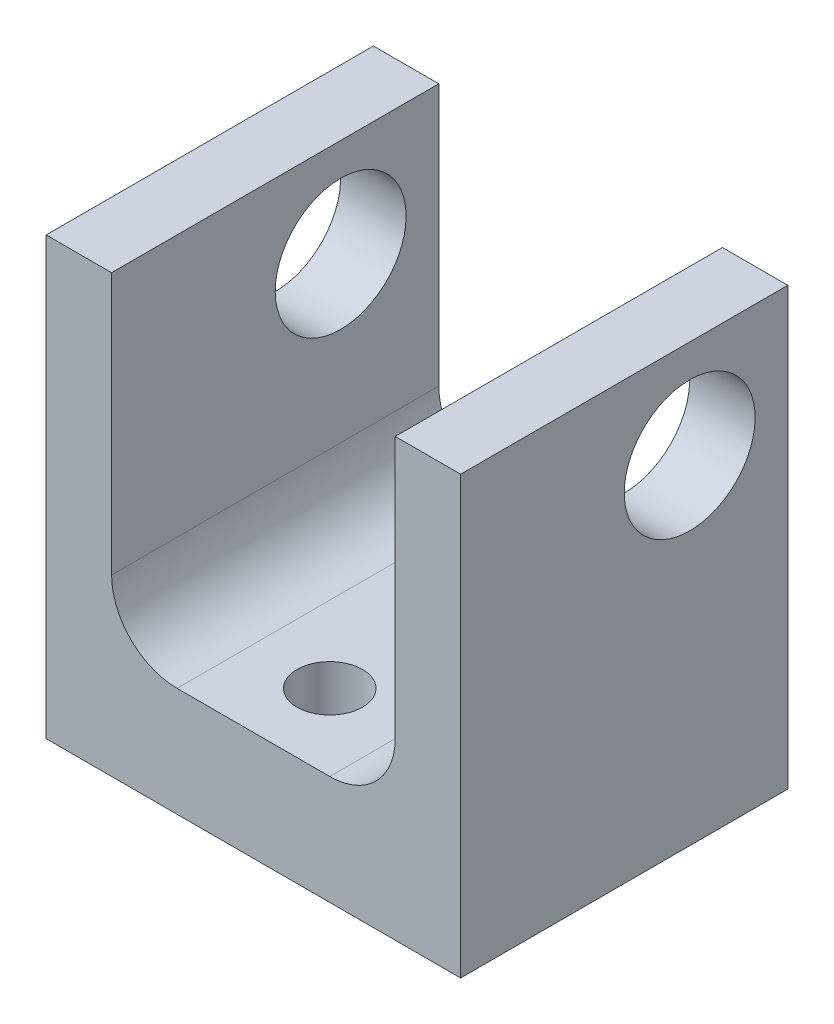
SolidWorks part; units mm, degrees
material "POM 乙缩醛共聚物"
ref_plane "前视基准面" through (0, 0, 0) normal (0, 0, 1) x (1, 0, 0)
ref_plane "上视基准面" through (0, 0, 0) normal (0, 1, 0) x (1, 0, 0)
ref_plane "右视基准面" through (0, 0, 0) normal (1, 0, 0) x (0, 0, -1)
sketch "草图1" plane through (0, 0, 0) normal (0, 0, 1) x (1, 0, 0)
  line L0 (0, 0) -> (0, 7.7911) construction
  line L1 (9.5, 0) -> (-9.5, 0)
  line L2 (-9.5, 0) -> (-9.5, 20)
  line L3 (9.5, 0) -> (9.5, 20)
  line L4 (-9.5, 20) -> (-6.5, 20)
  line L5 (9.5, 20) -> (6.5, 20)
  line L6 (-6.5, 20) -> (-6.5, 5)
  line L7 (6.5, 20) -> (6.5, 5)
  line L8 (-6.5, 5) -> (6.5, 5)
  point P12 (0, 5)
  dimension "D1" = 13
  dimension "D2" = 3
  dimension "D3" = 20
  dimension "D4" = 5
extrude "凸台-拉伸1" add sketch "草图1" along normal blind 15
fillet "圆角1" radius 3 2 edges at (-6.5, 5, 7.5) (6.5, 5, 7.5)
sketch "草图2" plane through (9.5, 0, 0) normal (1, 0, 0) x (0, 0, -1)
  line L0 (-4.5, 25) -> (-4.5, 0) construction
  line L2 (-15, 0) -> (0, 0) construction
  line L3 (0, 0) -> (0, 20) construction
  circle A0 centre (-4.5, 15.5) radius 3
  point P2 (0, 0)
  point P8 (0, 0)
  point P9 (0, 0)
  dimension "D1" = 15.5
  dimension "D2" = 6
  dimension "D3" = 4.5
extrude "切除-拉伸1" cut sketch "草图2" against normal through all
sketch "草图3" plane through (0, 5, 0) normal (0, 1, 0) x (1, 0, 0)
  line L0 (0, -15) -> (0, 0) construction
  line L1 (3.5, -15) -> (-3.5, -15) construction
  line L2 (9.5, -7.5) -> (-9.5, -7.5) construction
  line L3 (9.5, -15) -> (9.5, 0) construction
  line L4 (-9.5, -15) -> (-9.5, 0) construction
  circle A0 centre (0, -11.5) radius 1.5
  circle A1 centre (0, -3.5) radius 1.5
  dimension "D1" = 3
  dimension "D2" = 4
extrude "切除-拉伸2" cut sketch "草图3" against normal blind 10 contours A0
extrude "切除-拉伸3" cut sketch "草图3<3>" against normal blind 10
sketch "草图3<3>" plane through (0, 5, 0) normal (0, 1, 0) x (1, 0, 0) same geometry as "草图3"
